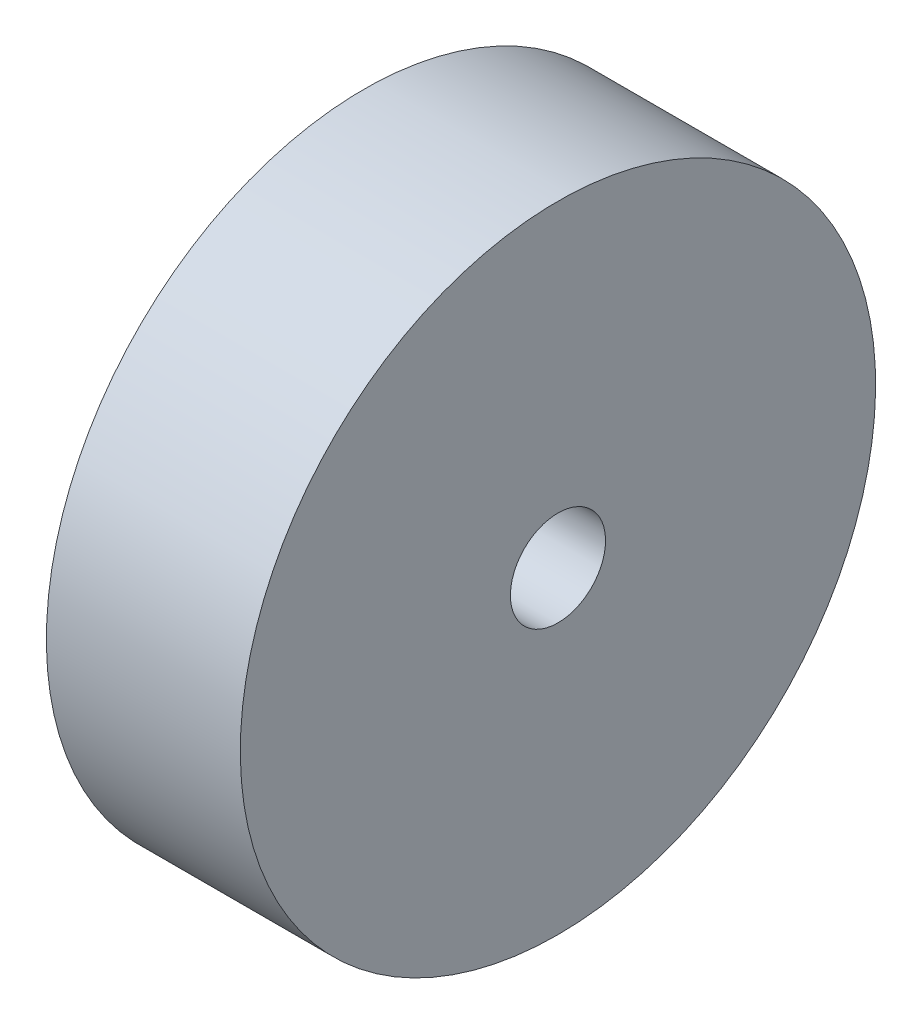
SolidWorks part; units mm, degrees
ref_plane "Front Plane" through (0, 0, 0) normal (0, 0, 1) x (1, 0, 0)
ref_plane "Top Plane" through (0, 0, 0) normal (0, 1, 0) x (1, 0, 0)
ref_plane "Right Plane" through (0, 0, 0) normal (1, 0, 0) x (0, 0, -1)
sketch "Sketch2" plane through (0, 0, 0) normal (0, 0, 1) x (1, 0, 0)
  line L0 (-78.8779, 0) -> (0, 0) construction
  line L3 (-13.25, 6.5) -> (-13.25, 43.4)
  line L4 (-13.25, 43.4) -> (13.25, 43.4)
  line L5 (13.25, 43.4) -> (13.25, 6.5)
  line L12 (0, 0) -> (78.8779, 0) construction
  line L13 (-33.465, 17.5) -> (33.465, 17.5) construction
  line L14 (-13.25, 6.5) -> (13.25, 6.5)
  line L15 (-33.465, 16) -> (33.465, 16) construction
  line L16 (0, -30.374) -> (0, 30.374) construction
  line L17 (-33.465, 12.5) -> (33.465, 12.5) construction
  point P12 (40.9654, 9.9331)
  point P15 (0, 16)
  point P16 (0, 17.5)
  point P19 (11.2701, 6.5)
  point P20 (0, 6.5)
  dimension "D1" = 13
  dimension "D2" = 86.8
  dimension "D3" = 26.5
  dimension "D4" = 16
  dimension "D5" = 12.5
  dimension "D7" = 17.5
revolve "Revolve1" add sketch "Sketch2" angle 360 about L0
